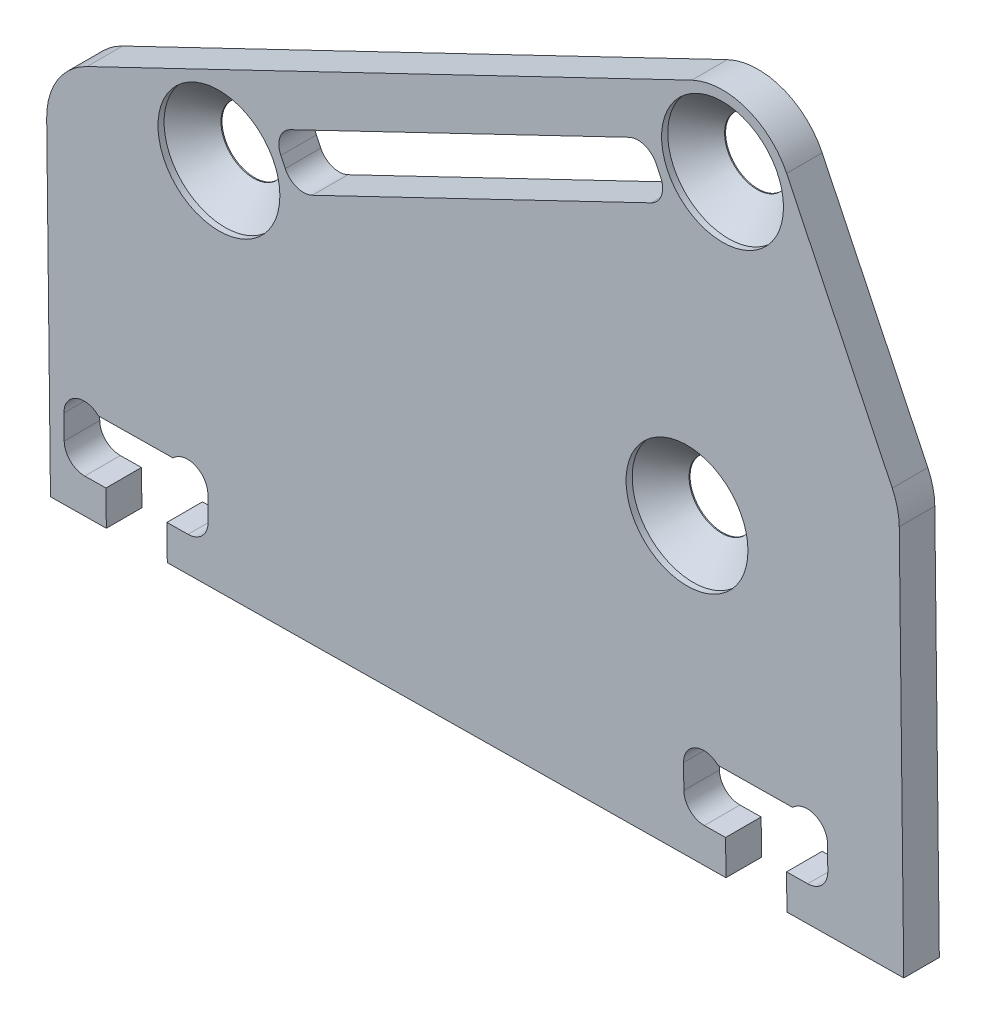
SolidWorks part; units mm, degrees
ref_plane "Front Plane" through (0, 0, 0) normal (0, 0, 1) x (1, 0, 0)
ref_plane "Top Plane" through (0, 0, 0) normal (0, 1, 0) x (1, 0, 0)
ref_plane "Right Plane" through (0, 0, 0) normal (1, 0, 0) x (0, 0, -1)
sketch "Sketch2" plane through (277.9441, -368.7823, 0) normal (0, 0, 1) x (0.9999, 0.0116, 0)
  line L0 (-273.6458, 371.9829) -> (-231.6458, 371.9829)
  line L1 (-237.0451, 403.462) -> (-231.9737, 392.5863)
  line L2 (-273.6458, 390.2567) -> (-231.6458, 390.2567) construction
  line L3 (-269.3958, 375.2829) -> (-238.8958, 375.2829) construction
  line L4 (-238.8958, 373.9829) -> (-238.8958, 371.9829) construction
  line L5 (-241.6964, 405.155) -> (-273.6458, 390.2567)
  line L6 (-273.6458, 390.2567) -> (-273.6458, 371.9829)
  line L7 (-242.1458, 376.5829) -> (-235.6458, 376.5829)
  line L8 (-265.1407, 390.3609) -> (-240.2172, 401.9829) construction
  line L9 (-260.534, 391.1298) -> (-243.7673, 398.9482)
  line L10 (-261.8629, 391.6135) -> (-262.0742, 392.0666)
  line L11 (-243.2836, 400.2771) -> (-243.4949, 400.7303)
  line L12 (-261.5905, 393.3955) -> (-244.8238, 401.214)
  line L13 (-261.4403, 390.7072) -> (-243.9175, 401.6366) construction
  line L14 (-270.1458, 388.0269) -> (-240.2172, 401.9829) construction
  line L15 (-242.861, 399.3708) -> (-262.4968, 392.9729) construction
  line L16 (-254.1458, 375.2829) -> (-254.1458, 371.9829) construction
  line L17 (-242.1458, 376.5829) -> (-242.1458, 373.9829)
  line L18 (-242.1458, 373.9829) -> (-235.6458, 373.9829)
  line L19 (-235.6458, 376.5829) -> (-235.6458, 373.9829)
  line L20 (-242.1458, 376.5829) -> (-235.6458, 373.9829) construction
  line L21 (-242.1458, 373.9829) -> (-235.6458, 376.5829) construction
  line L22 (-242.1458, 376.5829) -> (-239.5458, 373.9829) construction
  line L23 (-240.3958, 371.9829) -> (-237.3958, 371.9829)
  line L24 (-240.3958, 371.9829) -> (-240.3958, 373.9829)
  line L25 (-240.3958, 373.9829) -> (-237.3958, 373.9829)
  line L26 (-237.3958, 371.9829) -> (-237.3958, 373.9829)
  line L27 (-240.3958, 371.9829) -> (-237.3958, 373.9829) construction
  line L28 (-240.3958, 373.9829) -> (-237.3958, 371.9829) construction
  line L29 (-238.8958, 376.5829) -> (-238.8958, 373.9829) construction
  line L30 (-242.4387, 374.69) -> (-242.4387, 375.8758)
  line L31 (-235.3529, 375.8758) -> (-235.3529, 374.69)
  line L32 (-267.8958, 371.9829) -> (-267.8958, 373.9829)
  line L33 (-270.8958, 371.9829) -> (-270.8958, 373.9829)
  line L34 (-266.1458, 373.9829) -> (-272.6458, 373.9829)
  line L35 (-272.9387, 375.8758) -> (-272.9387, 374.69)
  line L36 (-266.1458, 376.5829) -> (-272.6458, 376.5829)
  line L37 (-265.8529, 374.69) -> (-265.8529, 375.8758)
  line L38 (-241.4387, 373.69) -> (-236.3529, 373.69)
  line L39 (-231.6458, 391.1072) -> (-231.6458, 371.9829)
  line L40 (-266.8529, 373.69) -> (-271.9387, 373.69)
  circle A0 centre (-242.1458, 386.4829) radius 1.6
  circle A1 centre (-265.1407, 390.3609) radius 1.6
  circle A2 centre (-240.2172, 401.9829) radius 1.6
  circle A3 centre (-270.1458, 388.0269) radius 3.5
  circle A4 centre (-240.2172, 401.9829) radius 3.5
  arc A5 (-262.0742, 392.0666) -> (-261.5905, 393.3955) centre (-261.1679, 392.4892) cw
  circle A6 centre (-235.1458, 391.1072) radius 3.5
  circle A7 centre (-241.4387, 375.8758) radius 1
  circle A8 centre (-236.3529, 375.8758) radius 1
  circle A9 centre (-236.3529, 374.69) radius 1
  circle A10 centre (-241.4387, 374.69) radius 1
  arc A11 (-261.8629, 391.6135) -> (-260.534, 391.1298) centre (-260.9566, 392.0361) ccw
  arc A12 (-243.7673, 398.9482) -> (-243.2836, 400.2771) centre (-244.1899, 399.8545) ccw
  circle A13 centre (-271.9387, 374.69) radius 1
  circle A14 centre (-271.9387, 375.8758) radius 1
  circle A15 centre (-266.8529, 375.8758) radius 1
  circle A16 centre (-266.8529, 374.69) radius 1
  arc A17 (-243.4949, 400.7303) -> (-244.8238, 401.214) centre (-244.4012, 400.3077) ccw
  spline S0 degree 3 poles (-273.6458, 390.2567) (-280.963, 386.8446) (-277.7104, 371.9829) (-273.6458, 371.9829) knots 0 0 0 0 1 1 1 1
  point P10 (-252.6789, 396.1719)
  point P15 (-240.2172, 401.9829)
  point P21 (-238.8958, 372.9829)
  point P91 (-276.0595, 373.69)
  point P93 (0, 0)
  dimension "D1" = 3.2
  dimension "D10" = 3
  dimension "D13" = 20.5
  dimension "D2" = 7
  dimension "D17" = 1
  dimension "D11" = 45
  dimension "D14" = 2
  dimension "D3" = 30
  dimension "D4" = 12
  dimension "D5" = 30.5
  dimension "D6" = 4.25
  dimension "D7" = 6.5
  dimension "D8" = 2.6
  dimension "D9" = 2
  dimension "D12" = 2.5
  dimension "D15" = 25
  dimension "D16" = 14.5
  dimension "D18" = 12
  dimension "D19" = 42
extrude "Boss-Extrude1" add sketch "Sketch2" along normal blind 1.75 contours A17 L11 A4 L5 A3 L6 L0 L39 A6 L1 A12 L9 A11 L10 A5 L12 A1 A0 | A3 | A6 | A4 A2 region at (22.3525, 12.8403, 0) region at (3.3136, 16.0836, 0) region at (34.2042, 33.5951, 0) region at (38.2755, 19.5698, 0)
sketch "Sketch3" plane through (0, 0, 1.75) normal (0, 0, 1) x (1, 0, 0)
  circle A0 centre (8.2913, 18.4755) radius 3
  circle A1 centre (31.3296, 14.8646) radius 3
  circle A2 centre (33.0782, 30.3859) radius 3
  dimension "D1" = 6
extrude "Cut-Extrude2" cut sketch "Sketch3" against normal blind 0.3
chamfer "Chamfer1" distance 1.4 angle 45 3 edges at (9.8913, 18.4755, 1.45) (32.9296, 14.8646, 1.45) (34.6782, 30.3859, 1.45)
